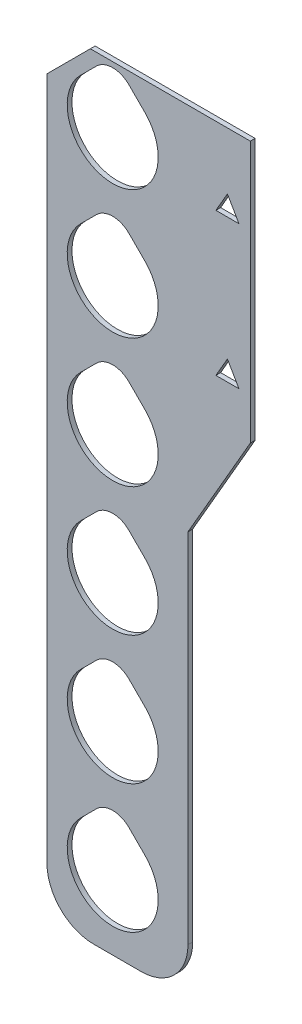
SolidWorks part; units mm, degrees
ref_plane "前视基准面" through (0, 0, 0) normal (0, 0, 1) x (1, 0, 0)
ref_plane "上视基准面" through (0, 0, 0) normal (0, 1, 0) x (1, 0, 0)
ref_plane "右视基准面" through (0, 0, 0) normal (1, 0, 0) x (0, 0, -1)
sketch "草图1" plane through (0, 0, 0) normal (0, 0, 1) x (1, 0, 0)
  line L0 (-3.3411, 10.0232) -> (-6.6822, 6.6822) construction
  line L1 (6.6822, 6.6822) -> (3.3411, 10.0232) construction
  line L2 (29.0767, 92.6495) -> (29.0767, 147.8038) construction
  line L3 (29.0767, 147.8038) -> (-4.7766, 147.8038) construction
  line L4 (-4.7766, 147.8038) -> (-14, 138.5805) construction
  line L5 (-14, 138.5805) -> (-14, -5) construction
  line L6 (-4, -15) -> (6, -15) construction
  line L7 (16, -5) -> (16, 70) construction
  line L8 (16, 70) -> (29.0767, 92.6495) construction
  line L9 (-3.3411, 37.0232) -> (-6.6822, 33.6822) construction
  line L10 (6.6822, 33.6822) -> (3.3411, 37.0232) construction
  line L11 (6.6822, 60.6822) -> (3.3411, 64.0232) construction
  line L12 (-3.3411, 64.0232) -> (-6.6822, 60.6822) construction
  line L13 (-3.3411, 91.0232) -> (-6.6822, 87.6822) construction
  line L21 (6.6822, 87.6822) -> (3.3411, 91.0232) construction
  line L22 (6.6822, 141.6822) -> (3.3411, 145.0232) construction
  line L23 (-3.3411, 145.0232) -> (-6.6822, 141.6822) construction
  line L24 (-3.3411, 118.0232) -> (-6.6822, 114.6822) construction
  line L25 (6.6822, 114.6822) -> (3.3411, 118.0232) construction
  line L26 (26.3284, 101.5038) -> (24.0767, 105.4038) construction
  line L27 (21.825, 101.5038) -> (26.3284, 101.5038) construction
  line L28 (24.0767, 105.4038) -> (21.825, 101.5038) construction
  line L29 (21.825, 131.5038) -> (26.3284, 131.5038) construction
  line L30 (24.0767, 135.4038) -> (21.825, 131.5038) construction
  line L31 (26.3284, 131.5038) -> (24.0767, 135.4038) construction
  line L32 (28.8767, 92.7031) -> (28.8767, 147.6038)
  line L33 (28.8767, 147.6038) -> (-4.6938, 147.6038)
  line L34 (-4.6938, 147.6038) -> (-13.8, 138.4976)
  line L35 (-13.8, 138.4976) -> (-13.8, -5)
  line L36 (-4, -14.8) -> (6, -14.8)
  line L37 (15.8, -5) -> (15.8, 70.0536)
  line L38 (15.8, 70.0536) -> (28.8767, 92.7031)
  line L39 (-3.4118, 10.0939) -> (-6.7529, 6.7529)
  line L40 (6.7529, 6.7529) -> (3.4118, 10.0939)
  line L41 (6.7529, 33.7529) -> (3.4118, 37.0939)
  line L42 (-3.4118, 37.0939) -> (-6.7529, 33.7529)
  line L43 (6.7529, 60.7529) -> (3.4118, 64.0939)
  line L44 (-3.4118, 64.0939) -> (-6.7529, 60.7529)
  line L45 (-3.4118, 91.0939) -> (-6.7529, 87.7529)
  line L46 (6.7529, 87.7529) -> (3.4118, 91.0939)
  line L47 (-3.4118, 118.0939) -> (-6.7529, 114.7529)
  line L48 (6.7529, 114.7529) -> (3.4118, 118.0939)
  line L49 (6.7529, 141.7529) -> (3.4118, 145.0939)
  line L50 (-3.4118, 145.0939) -> (-6.7529, 141.7529)
  line L51 (26.5016, 101.4038) -> (24.0767, 105.6038)
  line L52 (24.0767, 105.6038) -> (21.6518, 101.4038)
  line L53 (21.6518, 101.4038) -> (26.5016, 101.4038)
  line L54 (21.6518, 131.4038) -> (26.5016, 131.4038)
  line L55 (26.5016, 131.4038) -> (24.0767, 135.6038)
  line L56 (24.0767, 135.6038) -> (21.6518, 131.4038)
  arc A0 (-14, -5) -> (-4, -15) centre (-4, -5) ccw construction
  arc A1 (6, -15) -> (16, -5) centre (6, -5) ccw construction
  arc A2 (-6.6822, 6.6822) -> (6.6822, 6.6822) centre (0, 0) ccw construction
  arc A3 (3.3411, 10.0232) -> (-3.3411, 10.0232) centre (0, 6.6822) ccw construction
  arc A6 (3.3411, 37.0232) -> (-3.3411, 37.0232) centre (0, 33.6822) ccw construction
  arc A7 (-6.6822, 33.6822) -> (6.6822, 33.6822) centre (0, 27) ccw construction
  arc A8 (-6.6822, 60.6822) -> (6.6822, 60.6822) centre (0, 54) ccw construction
  arc A9 (3.3411, 64.0232) -> (-3.3411, 64.0232) centre (0, 60.6822) ccw construction
  arc A10 (3.3411, 91.0232) -> (-3.3411, 91.0232) centre (0, 87.6822) ccw construction
  arc A11 (-6.6822, 87.6822) -> (6.6822, 87.6822) centre (0, 81) ccw construction
  arc A12 (3.3411, 145.0232) -> (-3.3411, 145.0232) centre (0, 141.6822) ccw construction
  arc A13 (-6.6822, 141.6822) -> (6.6822, 141.6822) centre (0, 135) ccw construction
  arc A14 (3.3411, 118.0232) -> (-3.3411, 118.0232) centre (0, 114.6822) ccw construction
  arc A15 (-6.6822, 114.6822) -> (6.6822, 114.6822) centre (0, 108) ccw construction
  arc A16 (-13.8, -5) -> (-4, -14.8) centre (-4, -5) ccw
  arc A17 (6, -14.8) -> (15.8, -5) centre (6, -5) ccw
  arc A18 (-6.7529, 6.7529) -> (6.7529, 6.7529) centre (0, 0) ccw
  arc A19 (3.4118, 10.0939) -> (-3.4118, 10.0939) centre (0, 6.6822) ccw
  arc A20 (-6.7529, 33.7529) -> (6.7529, 33.7529) centre (0, 27) ccw
  arc A21 (3.4118, 37.0939) -> (-3.4118, 37.0939) centre (0, 33.6822) ccw
  arc A22 (3.4118, 64.0939) -> (-3.4118, 64.0939) centre (0, 60.6822) ccw
  arc A23 (-6.7529, 60.7529) -> (6.7529, 60.7529) centre (0, 54) ccw
  arc A24 (-6.7529, 87.7529) -> (6.7529, 87.7529) centre (0, 81) ccw
  arc A25 (3.4118, 91.0939) -> (-3.4118, 91.0939) centre (0, 87.6822) ccw
  arc A26 (-6.7529, 114.7529) -> (6.7529, 114.7529) centre (0, 108) ccw
  arc A27 (3.4118, 118.0939) -> (-3.4118, 118.0939) centre (0, 114.6822) ccw
  arc A28 (3.4118, 145.0939) -> (-3.4118, 145.0939) centre (0, 141.6822) ccw
  arc A29 (-6.7529, 141.7529) -> (6.7529, 141.7529) centre (0, 135) ccw
  dimension "D1" = 0.2
  dimension "D2" = 0.1
  dimension "D3" = 0.1
  dimension "D4" = 0.1
  dimension "D5" = 0.1
  dimension "D6" = 0.1
  dimension "D7" = 0.1
  dimension "D8" = 0.1
  dimension "D9" = 0.1
extrude "凸台-拉伸1" add sketch "草图1" along normal blind 1 contours L36 A17 L37 L38 L32 L33 L34 L35 A16 L31 L29 L30 L28 L26 L27 A3 L1 A2 L0 A7 L9 A6 L10 A9 L11 A8 L12 A11 L13 A10 L21 A13 L23 A12 L22 A15 L24 A14 L25 | L32 L33 L34 L35 A16 L36 A17 L37 L38 | L39 A18 L40 A19 | A20 L41 A21 L42 | L43 A22 L44 A23 | L45 A24 L46 A25 | L47 A26 L48 A27 | L49 A28 L50 A29 | L54 L55 L56 | L51 L52 L53 region at (20.8841, 82.2179, 0)
